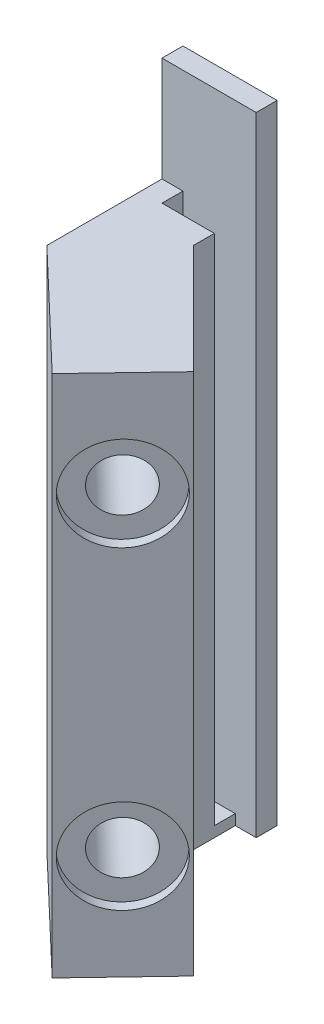
SolidWorks part; units mm, degrees
ref_plane "Front" through (0, 0, 0) normal (0, 0, 1) x (1, 0, 0)
ref_plane "Top" through (0, 0, 0) normal (0, 1, 0) x (1, 0, 0)
ref_plane "Right" through (0, 0, 0) normal (1, 0, 0) x (0, 0, -1)
other "Configuration Table"
sketch "Sketch1" plane through (0, 0, 0) normal (0, 1, 0) x (1, 0, 0)
  line L0 (0, 0) -> (0, -6)
  line L1 (0, -6) -> (7, -6)
  line L2 (7, -6) -> (7, -4)
  line L3 (7, -4) -> (2, -4)
  line L4 (0, 0) -> (9, 0)
  line L5 (9, 0) -> (9, -2)
  line L6 (9, -2) -> (2, -2)
  line L7 (2, -2) -> (2, -4)
  dimension "D1" = 6
  dimension "D2" = 7
  dimension "D3" = 2
  dimension "D4" = 2
  dimension "D5" = 7
  dimension "D6" = 9
extrude "Boss-Extrude1" add sketch "Sketch1" along normal blind 50
sketch "Sketch2" plane through (0, 50, 0) normal (0, 1, 0) x (1, 0, 0)
  line L1 (9, -2) -> (0, -2)
  line L2 (9, -2) -> (9, 0)
  line L3 (9, 0) -> (0, 0)
  line L4 (0, -2) -> (0, 0)
extrude "Boss-Extrude2" add sketch "Sketch2" along normal blind 10
sketch "Sketch3" plane through (0, 0, 0) normal (0, 0, -1) x (-1, 0, 0)
  line L0 (0, 60) -> (0, 0) construction
  line L1 (-9, 60) -> (0, 60) construction
  circle A0 centre (-5.5, 55) radius 3.15
  dimension "D1" = 6.3
  dimension "D2" = 5.5
  dimension "D3" = 5
extrude "Cut-Extrude1" cut sketch "Sketch3" against normal blind 1
sketch "Sketch4" plane through (0, 0, 0) normal (0, -1, 0) x (1, 0, 0)
  line L0 (7, 6) -> (0, 13)
  line L1 (0, 13) -> (0, 6)
  line L2 (0, 6) -> (7, 6) construction
  line L3 (0, 13) -> (10.8579, 23.3492)
  line L4 (10.8579, 23.3492) -> (17.4417, 16.4417)
  line L5 (17.4417, 16.4417) -> (7, 6)
  line M8 (7, 6) -> (0, 6)
  dimension "D1" = 7
  dimension "D2" = 15
extrude "Boss-Extrude3" add sketch "Sketch4" against normal blind 50 contours L5 L4 L3 L0 | L0 L1 M8 region at (2.3333, 0, 8.3333) region at (8.7835, 0, 14.675)
sketch "Sketch5" plane through (0, 0, 0) normal (0, -1, 0) x (1, 0, 0)
  line L1 (2, 2) -> (7, 2)
  line L2 (2, 2) -> (2, 4)
  line L3 (2, 4) -> (7, 4)
  line L4 (7, 2) -> (7, 4)
extrude "Boss-Extrude4" add sketch "Sketch5" against normal blind 1
sketch "Sketch6" plane through (17.3504, 0, 16.5375) normal (0.7239, 0, 0.6899) x (0.6899, 0, -0.7239)
  line L0 (-4.6389, 50) -> (-4.6389, 0) construction
  line L1 (-9.4102, 50) -> (0.1323, 50) construction
  line L2 (-9.4102, 0) -> (0.1323, 0) construction
  circle A0 centre (-4.6389, 40) radius 2.5
  circle A1 centre (-4.6389, 10) radius 2.5
  circle A2 centre (-4.6389, 40) radius 4.5
  circle A3 centre (-4.6389, 10) radius 4.5
  dimension "D1" = 5
  dimension "D2" = 5
  dimension "D3" = 9
  dimension "D4" = 9
  dimension "D5" = 10
  dimension "D6" = 10
extrude "Cut-Extrude2" cut sketch "Sketch6" against normal blind 1
extrude "Cut-Extrude3" cut sketch "Sketch6<2>" against normal through all contours L0 A0 | A0 L0 | L0 A1 | A1 L0 region at (14.8819, 40, 19.1274) region at (13.4178, 40, 20.6635) region at (14.8819, 10, 19.1274) region at (13.4178, 10, 20.6635)
sketch "Sketch6<2>" plane through (17.3504, 0, 16.5375) normal (0.7239, 0, 0.6899) x (0.6899, 0, -0.7239) same geometry as "Sketch6"
